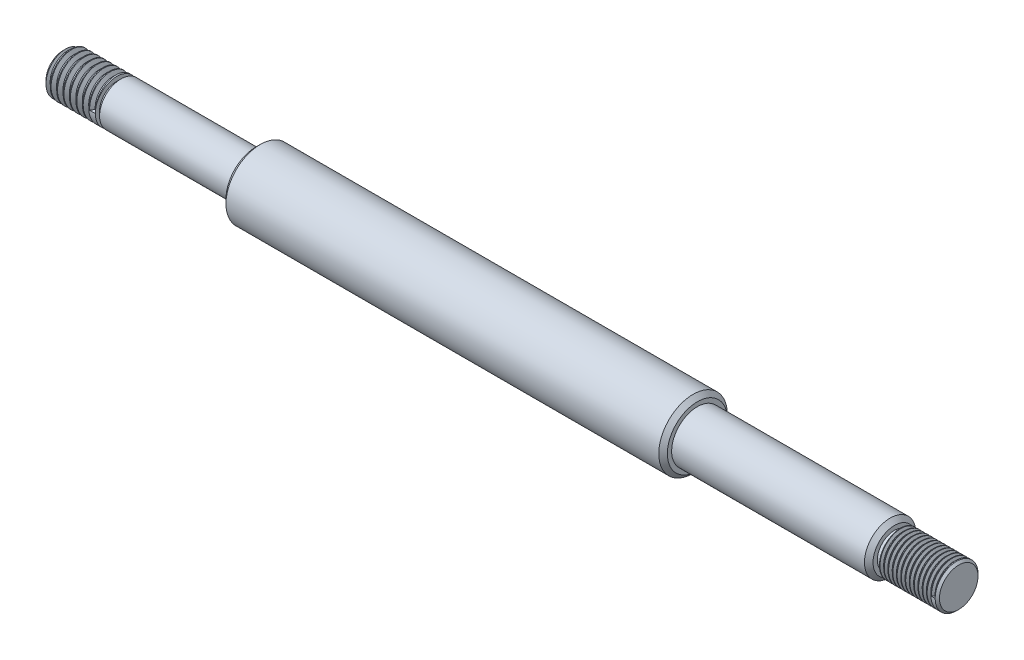
SolidWorks part; units mm, degrees
note: '?' marks a value the reader was unsure of.
ref_plane "Front Plane" through (0, 0, 0) normal (0, 0, 1) x (1, 0, 0)
ref_plane "Top Plane" through (0, 0, 0) normal (0, 1, 0) x (1, 0, 0)
ref_plane "Right Plane" through (0, 0, 0) normal (1, 0, 0) x (0, 0, -1)
ref_axis "X" through (-88.99, 0, 0) along (1, 0, 0)?
ref_axis "Y" through (0, 0, -88.99) along (0, 0, 1)?
ref_axis "Z" through (0, 55, 0) along (0, -1, 0)?
sketch "Sketch1" plane through (0, 0, 0) normal (0, 0, 1) x (1, 0, 0)
  line L0 (-104.5, 0) -> (-32.106, 0) construction
  line L1 (-104.5, 0) -> (-104.5, 5)
  line L4 (104.5, 0) -> (-104.5, 0)
  line L6 (43.5, 6) -> (89.5, 6)
  line L13 (-59.5, 8) -> (43.5, 8)
  line L19 (-104.5, 5) -> (-92, 5)
  line L20 (-59.5, 5) -> (-59.5, 8)
  line L21 (43.5, 6) -> (43.5, 8)
  line L22 (90.5, 5) -> (104.5, 5)
  line L25 (104.5, 0) -> (104.5, 5)
  line L27 (-88.99, 0) -> (88.99, 0) construction
  line L28 (-91, 5) -> (-59.5, 5)
  line L31 (89.5, 6) -> (89.5, 4)
  line L32 (89.5, 4) -> (90.5, 4)
  line L33 (90.5, 5) -> (90.5, 4)
  line L35 (-91, 5) -> (-91, 4)
  line L36 (-91, 4) -> (-92, 4)
  line L37 (-92, 5) -> (-92, 4)
  point P11 (90.5, 4.5)
  point P20 (0, 0)
  dimension "D12" = 1
  dimension "D10" = 1
  dimension "D2" = 45
  dimension "D3" = 6
  dimension "D4" = 14
  dimension "D5" = 61
  dimension "D6" = 16
  dimension "D7" = 103
  dimension "D8" = 5
  dimension "D9" = 10
  dimension "D11" = 5
  dimension "D13" = 1
  dimension "D14" = 1
  dimension "D15" = 12.5
revolve "Revolve1" add sketch "Sketch1" angle 360 about L0
ref_plane "Plane1" through (0, 0, 0) normal (1, 0, 0) x (0, 0, -1)
chamfer "Chamfer1" distance 0.5 angle 45 1 edges at (104.5, -5, 0)
thread "Thread1" pitch 1 method cut profile "Thread Profile1" start angle 0, offset 0, length 0, pitch 1, diameter 10
ref_plane "Plane2" through (104, 0, 5) normal (0, -1, 0) x (0, 0, 1)
sketch "Thread Profile1" plane through (104, 0, 5) normal (0, -1, 0) x (0, 0, 1)
  line L0 (0, 0) -> (0, 1) construction
  line L11 (0, 0) -> (0, 0.875)
  line L12 (0, 0.875) -> (-0.5413, 0.5625)
  line L13 (-0.5413, 0.5625) -> (-0.5413, 0.3125)
  line L15 (-0.5413, 0.3125) -> (0, 0)
  line L17 (-0.5413, 0.4375) -> (0, 0.4375) construction
  point P2 (0, 0)
  dimension "Pitch" = 1
  dimension "Profile_Angle" = 60
  dimension "Profile_Land" = 0.25
  dimension "Profile_Height" = 0.5413
chamfer "Chamfer2" distance 1 angle 45 1 edges at (-104.5, -5, 0)
thread "Thread2" pitch 1.5 method cut profile "Thread Profile2" start angle 0, offset 0, length 0, pitch 1.5, diameter 10
ref_plane "Plane3" through (-92, 0, 5) normal (0, -1, 0) x (0, 0, 1)
sketch "Thread Profile2" plane through (-92, 0, 5) normal (0, -1, 0) x (0, 0, 1)
  line L0 (0, 0) -> (0, 1.5) construction
  line L11 (0, 0) -> (0, 1.3125)
  line L12 (0, 1.3125) -> (-0.8119, 0.8437)
  line L13 (-0.8119, 0.8437) -> (-0.8119, 0.4687)
  line L15 (-0.8119, 0.4687) -> (0, 0)
  line L17 (-0.8119, 0.6562) -> (0, 0.6562) construction
  point P2 (0, 0)
  dimension "Pitch" = 1.5
  dimension "Profile_Angle" = 60
  dimension "Profile_Land" = 0.375
  dimension "Profile_Height" = 0.8119
chamfer "Chamfer3" distance 1 angle 45 3 edges at (89.5, -6, 0) (43.5, -8, 0) (-59.5, -8, 0)
